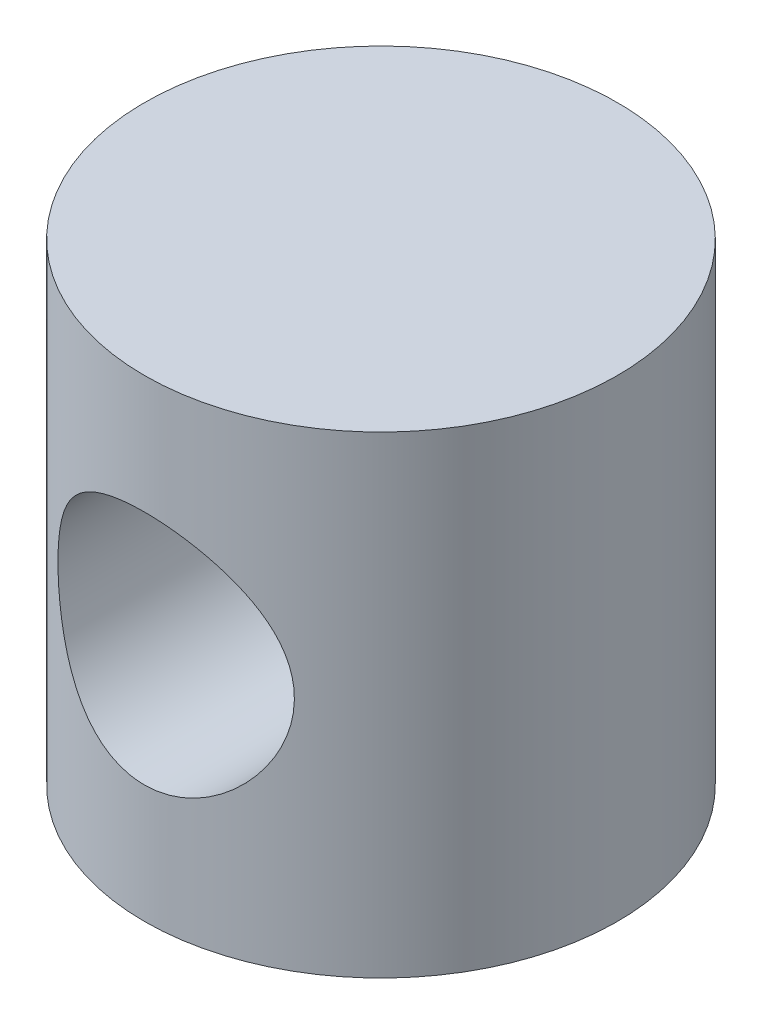
SolidWorks part; units mm, degrees
ref_plane "Front Plane" through (0, 0, 0) normal (0, 0, 1) x (1, 0, 0)
ref_plane "Top Plane" through (0, 0, 0) normal (0, 1, 0) x (1, 0, 0)
ref_plane "Right Plane" through (0, 0, 0) normal (1, 0, 0) x (0, 0, -1)
sketch "Sketch1" plane through (0, 0, 0) normal (0, 1, 0) x (1, 0, 0)
  circle A0 centre (0, 0) radius 5
  dimension "D1" = 10
extrude "Boss-Extrude1" add sketch "Sketch1" along normal blind 10
sketch "Sketch2" plane through (0, 0, 0) normal (0, 0, 1) x (1, 0, 0)
  circle A0 centre (0, 5) radius 2.5
  point P2 (0, 0)
  dimension "D2" = 5
  dimension "D1" = 5
extrude "Cut-Extrude1" cut sketch "Sketch2" along normal through all
